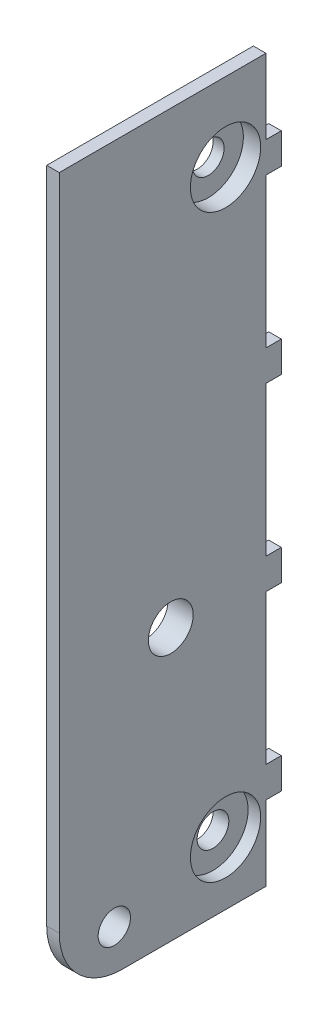
SolidWorks part; units mm, degrees
ref_plane "Front Plane" through (0, 0, 0) normal (0, 0, 1) x (1, 0, 0)
ref_plane "Top Plane" through (0, 0, 0) normal (0, 1, 0) x (1, 0, 0)
ref_plane "Right Plane" through (0, 0, 0) normal (1, 0, 0) x (0, 0, -1)
sketch "Sketch1" plane through (0, 0, 0) normal (0, 0, 1) x (1, 0, 0)
  line L1 (-100, -115) -> (100, -115)
  line L2 (-100, -115) -> (-100, 115)
  line L3 (-100, 115) -> (100, 115)
  line L4 (100, -115) -> (100, 115)
  line L5 (-100, -115) -> (100, 115) construction
  line L6 (-100, 115) -> (100, -115) construction
  point P0 (0, 0)
  dimension "D1" = 230
  dimension "D2" = 200
extrude "Boss-Extrude1" add sketch "Sketch1" along normal blind 70
sketch "Sketch2" plane through (0, 0, 70) normal (0, 0, 1) x (1, 0, 0)
  line L0 (100, 115) -> (-100, 115) construction
  line L1 (-96, -111) -> (96, -111)
  line L2 (-96, -111) -> (-96, 111)
  line L3 (-96, 111) -> (96, 111)
  line L4 (96, -111) -> (96, 111)
  line L5 (-96, -111) -> (96, 111) construction
  line L6 (-96, 111) -> (96, -111) construction
  line L7 (-100, 115) -> (-100, -115) construction
  point P0 (0, 0)
  dimension "D1" = 4
  dimension "D2" = 4
extrude "Cut-Extrude1" cut sketch "Sketch2" against normal blind 66
sketch "Sketch4" plane through (0, -115, 0) normal (0, -1, 0) x (1, 0, 0)
  line L0 (-100, 70) -> (-100, 0) construction
  line L1 (-98, 45) -> (98, 45)
  line L2 (-98, 45) -> (-98, 70)
  line L3 (-98, 70) -> (98, 70)
  line L4 (98, 45) -> (98, 70)
  line L5 (100, 70) -> (100, 0) construction
  line L6 (-100, 70) -> (100, 70) construction
  dimension "D1" = 2
  dimension "D2" = 2
  dimension "D3" = 0
  dimension "D4" = 25
extrude "Cut-Extrude3" cut sketch "Sketch4" against normal blind 10
sketch "Sketch10" plane through (0, 0, 4) normal (0, 0, 1) x (1, 0, 0)
  line L0 (-96, 111) -> (-96, -111) construction
  line L1 (-96, -111) -> (96, -111) construction
  circle A0 centre (0, -11) radius 5
  dimension "D1" = 10
  dimension "D2" = 96
  dimension "D3" = 100
extrude "Cut-Extrude8" cut sketch "Sketch10" against normal through all
sketch "Sketch11" plane through (0, 0, 70) normal (0, 0, 1) x (1, 0, 0)
  line L0 (-98, -105) -> (-98, -115) construction
  line L1 (-98, -105) -> (-100, -105)
  line L2 (-98, -105) -> (-98, -115)
  line L3 (-98, -115) -> (-100, -115)
  line L4 (-100, -105) -> (-100, -115)
  dimension "D1" = 10
extrude "Boss-Extrude2" add sketch "Sketch11" along normal blind 20
sketch "Sketch12" plane through (0, 0, 90) normal (0, 0, 1) x (1, 0, 0)
  line L0 (-100, -105) -> (-100, -115) construction
  line L1 (-100, -107.5) -> (-98, -107.5)
  line L2 (-100, -107.5) -> (-100, -112.5)
  line L3 (-100, -112.5) -> (-98, -112.5)
  line L4 (-98, -107.5) -> (-98, -112.5)
  line L5 (-98, -115) -> (-98, -105) construction
  line L6 (-98, -105) -> (-100, -105) construction
  dimension "D1" = 2.5
  dimension "D2" = 5
extrude "Cut-Extrude9" cut sketch "Sketch12" against normal blind 20
fillet "Fillet1" radius 2.5 2 edges at (-99, -112.5, 70) (-99, -107.5, 70)
sketch "Sketch13" plane through (0, 0, 70) normal (0, 0, 1) x (1, 0, 0)
  line L0 (98, -115) -> (100, -115) construction
  line L1 (98, -105) -> (100, -105)
  line L2 (98, -105) -> (98, -115)
  line L3 (98, -115) -> (100, -115)
  line L4 (100, -105) -> (100, -115)
  dimension "D1" = 0
  dimension "D2" = 2
extrude "Boss-Extrude3" add sketch "Sketch13" along normal blind 20
sketch "Sketch14" plane through (0, 0, 90) normal (0, 0, 1) x (1, 0, 0)
  line L0 (98, -105) -> (98, -115) construction
  line L1 (98, -107.5) -> (100, -107.5)
  line L2 (98, -107.5) -> (98, -112.5)
  line L3 (98, -112.5) -> (100, -112.5)
  line L4 (100, -107.5) -> (100, -112.5)
  line L5 (100, -115) -> (100, -105) construction
  line L6 (98, -105) -> (96, -105) construction
  dimension "D1" = 2.5
  dimension "D2" = 5
extrude "Cut-Extrude10" cut sketch "Sketch14" against normal blind 20
fillet "Fillet2" radius 2.5 2 edges at (99, -112.5, 70) (99, -107.5, 70)
sketch "Sketch15" plane through (0, 115, 0) normal (0, 1, 0) x (1, 0, 0)
  line L0 (100, -70) -> (-100, -70) construction
  line L1 (96, -70) -> (-96, -70)
  line L2 (96, -70) -> (96, -4)
  line L3 (96, -4) -> (-96, -4)
  line L4 (-96, -70) -> (-96, -4)
  line L5 (-100, -70) -> (-100, 0) construction
  line L6 (100, -70) -> (100, 0) construction
  line L7 (100, 0) -> (-100, 0) construction
  dimension "D1" = 4
  dimension "D2" = 4
  dimension "D3" = 4
extrude "Cut-Extrude11" cut sketch "Sketch15" against normal through all
sketch "Sketch16" plane through (-98, 0, 0) normal (1, 0, 0) x (0, 0, -1)
  line L0 (-90, -107.5) -> (-72.5, -107.5)
  line L1 (-72.5, -112.5) -> (-90, -112.5)
  line L2 (-90, -112.5) -> (-90, -115)
  line L3 (-90, -115) -> (-45, -115)
  line L4 (-45, -115) -> (-45, -105)
  line L5 (-45, -105) -> (-90, -105)
  line L6 (-90, -105) -> (-90, -107.5)
  arc A0 (-72.5, -107.5) -> (-72.5, -112.5) centre (-72.5, -110) cw
extrude "Boss-Extrude4" add sketch "Sketch16" along normal blind 2
sketch "Sketch18" plane through (100, 0, 0) normal (1, 0, 0) x (0, 0, -1)
  line L0 (-70, -105) -> (-70, 115) construction
  line L1 (-70, 115) -> (0, 115) construction
  circle A0 centre (-34.45, -28.4) radius 7.15
  dimension "D2" = 14.3
  dimension "D1" = 35.55
  dimension "D3" = 143.4
extrude "Cut-Extrude12" cut sketch "Sketch18" against normal through all
sketch "Sketch19" plane through (100, 0, 0) normal (1, 0, 0) x (0, 0, -1)
  line L0 (-90, -115) -> (0, -115) construction
  line L1 (0, -115) -> (0, 115) construction
  circle A0 centre (-17, -95) radius 5.05
  dimension "D1" = 10.1
  dimension "D2" = 20
  dimension "D3" = 17
extrude "Cut-Extrude13" cut sketch "Sketch19" against normal through all
sketch "Sketch20" plane through (100, 0, 0) normal (1, 0, 0) x (0, 0, -1)
  line L0 (-70, 115) -> (0, 115) construction
  line L1 (0, -115) -> (0, 115) construction
  circle A0 centre (-17, 90) radius 5.05
  dimension "D1" = 10.1
  dimension "D2" = 25
  dimension "D3" = 17
extrude "Cut-Extrude14" cut sketch "Sketch20" against normal through all
sketch "Sketch17" plane through (98, 0, 0) normal (-1, 0, 0) x (0, 0, 1)
  line L0 (90, -107.5) -> (72.5, -107.5)
  line L1 (72.5, -112.5) -> (90, -112.5)
  line L2 (90, -112.5) -> (90, -115)
  line L3 (90, -115) -> (45, -115)
  line L4 (45, -115) -> (45, -105)
  line L5 (45, -105) -> (90, -105)
  line L6 (90, -105) -> (90, -107.5)
  arc A0 (72.5, -107.5) -> (72.5, -112.5) centre (72.5, -110) ccw
extrude "Boss-Extrude5" add sketch "Sketch17" along normal blind 2
sketch "Sketch21" plane through (100, 0, 0) normal (1, 0, 0) x (0, 0, -1)
  line L1 (-90, -115) -> (-70, -115)
  line L2 (-90, -115) -> (-90, -105)
  line L3 (-90, -105) -> (-70, -105)
  line L4 (-70, -115) -> (-70, -105)
extrude "Cut-Extrude15" cut sketch "Sketch21" against normal through all
sketch "Sketch22" plane through (0, 0, 4) normal (0, 0, 1) x (1, 0, 0)
  line L0 (96, 115) -> (-96, 115) construction
  line L1 (46, 75) -> (-46, 75)
  line L2 (46, 75) -> (46, 115)
  line L3 (46, 115) -> (-46, 115)
  line L4 (-46, 75) -> (-46, 115)
  line L5 (96, -115) -> (96, 115) construction
  line L6 (-96, 115) -> (-96, -115) construction
  dimension "D1" = 50
  dimension "D2" = 50
  dimension "D3" = 40
extrude "Cut-Extrude16" cut sketch "Sketch22" against normal blind 10
sketch "Sketch24" plane through (100, 0, 0) normal (1, 0, 0) x (0, 0, -1)
  line L0 (-70, -115) -> (-70, 115) construction
  line L1 (-70, -115) -> (0, -115) construction
  circle A0 centre (-52.45, -102) radius 5.15
  dimension "D1" = 10.3
  dimension "D2" = 17.55
  dimension "D3" = 13
extrude "Cut-Extrude18" cut sketch "Sketch24" against normal through all
fillet "Fillet3" radius 20 1 edges at (98, -115, 70)
fillet "Fillet4" radius 20 1 edges at (-98, -115, 70)
sketch "Sketch25" plane through (0, 115, 0) normal (0, 1, 0) x (1, 0, 0)
  line L0 (-100, -70) -> (-100, 0) construction
  line L1 (100, 0) -> (-100, 0)
  line L2 (100, 0) -> (100, -4.1191)
  line L3 (100, -4.1191) -> (-100, -4.1191)
  line L4 (-100, 0) -> (-100, -4.1191)
extrude "Cut-Extrude19" cut sketch "Sketch25" against normal through all
sketch "Sketch26" plane through (0, 115, 0) normal (0, 1, 0) x (1, 0, 0)
  line L1 (-96, -70) -> (-100, -70)
  line L2 (-96, -70) -> (-96, -4.1191)
  line L3 (-96, -4.1191) -> (-100, -4.1191)
  line L4 (-100, -70) -> (-100, -4.1191)
extrude "Cut-Extrude20" cut sketch "Sketch26" against normal through all
sketch "Sketch27" plane through (0, 0, 4.1191) normal (0, 0, -1) x (-1, 0, 0)
  line L0 (-100, -115) -> (-100, 115) construction
  line L1 (-100, -91.15) -> (-96, -91.15)
  line L2 (-100, -91.15) -> (-100, -81.35)
  line L3 (-100, -81.35) -> (-96, -81.35)
  line L4 (-96, -91.15) -> (-96, -81.35)
  line L5 (-96, 115) -> (-96, -115) construction
  line L6 (-96, -115) -> (-100, -115) construction
  dimension "D1" = 9.8
  dimension "D2" = 23.85
extrude "Boss-Extrude6" add sketch "Sketch27" along normal blind 4.9
sketch "Sketch28" plane through (0, 0, 4.1191) normal (0, 0, -1) x (-1, 0, 0)
  line L0 (-100, -81.35) -> (-100, 115) construction
  line L1 (-100, -23.85) -> (-96, -23.85)
  line L2 (-100, -23.85) -> (-100, -33.65)
  line L3 (-100, -33.65) -> (-96, -33.65)
  line L4 (-96, -23.85) -> (-96, -33.65)
  line L5 (-96, 115) -> (-96, -81.35) construction
  line L6 (-96, -115) -> (-100, -115) construction
  dimension "D2" = 9.8
  dimension "D3" = 81.35
extrude "Boss-Extrude7" add sketch "Sketch28" along normal blind 4.9
ref_plane "Plane1" through (0, 0, 0) normal (0, 1, 0) x (1, 0, 0)
mirror "Mirror1" about plane through (0, 0, 0) normal (0, 1, 0) of "Boss-Extrude7", "Boss-Extrude6"
sketch "Sketch29" plane through (96, 0, 0) normal (-1, 0, 0) x (0, 0, 1)
  circle A0 centre (17, 90) radius 12.5
  circle A1 centre (17, 90) radius 5.05
  dimension "D1" = 10.1
  dimension "D2" = 25
extrude "Boss-Extrude8" add sketch "Sketch29" along normal blind 5
sketch "Sketch30" plane through (96, 0, 0) normal (-1, 0, 0) x (0, 0, 1)
  circle A0 centre (52.45, -102) radius 5.15
  circle A1 centre (52.45, -102) radius 8.5
  dimension "D1" = 10.3
  dimension "D2" = 17
extrude "Boss-Extrude9" add sketch "Sketch30" along normal blind 5
sketch "Sketch31" plane through (96, 0, 0) normal (-1, 0, 0) x (0, 0, 1)
  circle A0 centre (34.45, -28.4) radius 7.15
  circle A1 centre (34.45, -28.4) radius 10
  dimension "D1" = 14.3
  dimension "D2" = 20
extrude "Boss-Extrude10" add sketch "Sketch31" along normal blind 4
sketch "Sketch32" plane through (100, 0, 0) normal (1, 0, 0) x (0, 0, -1)
  circle A0 centre (-17, -95) radius 11.2
  dimension "D1" = 22.4
extrude "Cut-Extrude21" cut sketch "Sketch32" against normal blind 5.5
ref_plane "Plane2" through (0, -2.5, 0) normal (0, 1, 0) x (1, 0, 0)
mirror "Mirror4" about plane through (0, -2.5, 0) normal (0, 1, 0) of "Boss-Extrude8"
mirror "Mirror5" about plane through (0, -2.5, 0) normal (0, 1, 0) of "Cut-Extrude21"
